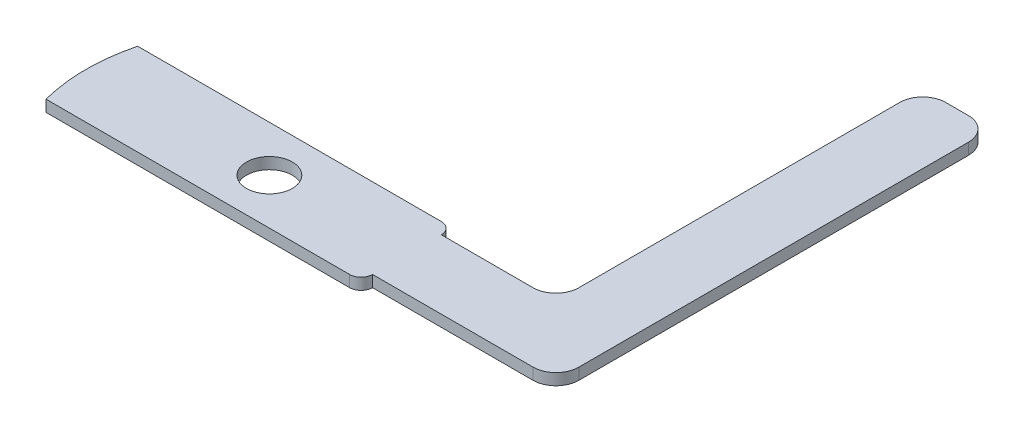
SolidWorks part; units mm, degrees
ref_plane "Front Plane" through (0, 0, 0) normal (0, 0, 1) x (1, 0, 0)
ref_plane "Top Plane" through (0, 0, 0) normal (0, 1, 0) x (1, 0, 0)
ref_plane "Right Plane" through (0, 0, 0) normal (1, 0, 0) x (0, 0, -1)
sketch "Sketch1" plane through (0, 0, 0) normal (0, 1, 0) x (1, 0, 0)
  line L0 (0, 6.35) -> (-31.75, 6.35) construction
  line L1 (0, 0) -> (-31.75, 0)
  line L2 (0, 0) -> (0, 12.7)
  line L3 (0, 12.7) -> (-31.75, 12.7)
  line L4 (-31.75, 0) -> (-31.75, 12.7) construction
  line L5 (0, 12.7) -> (12.7, 12.7)
  line L6 (12.7, 12.7) -> (12.7, 11.1125)
  line L7 (12.7, 11.1125) -> (28.575, 11.1125)
  line L8 (38.1, 11.1125) -> (38.1, 1.5875)
  line L9 (38.1, 1.5875) -> (12.7, 1.5875)
  line L10 (12.7, 1.5875) -> (12.7, 0)
  line L11 (12.7, 0) -> (0, 0)
  line L12 (38.1, 11.1125) -> (38.1, 61.9125)
  line L13 (38.1, 61.9125) -> (28.575, 61.9125)
  line L14 (28.575, 61.9125) -> (28.575, 11.1125)
  line L15 (28.575, 11.1125) -> (38.1, 11.1125) construction
  circle A0 centre (-6.35, 6.35) radius 3.175
  arc A1 (-30.9434, 12.7) -> (-30.9434, 0) centre (-6.35, 6.35) ccw
  dimension "D4" = 6.35
  dimension "D1" = 12.7
  dimension "D2" = 31.75
  dimension "D3" = 6.35
  dimension "D5" = 12.7
  dimension "D6" = 25.4
  dimension "D7" = 9.525
  dimension "D8" = 50.8
extrude "Boss-Extrude1" add sketch "Sketch1" along normal blind 1.5875 contours L2 L0 A0 L4 L1 | L0 L2 L3 L4 A0 | L11 L10 L9 L8 L6 L5 L2 region at (-16.5503, 0, -6.35) region at (0.727, 0, -6.35)
fillet "Fillet1" radius 3.175 4 edges at (38.1, 0.7937, -61.9125) (28.575, 0.7937, -61.9125) (28.575, 0.7937, -11.1125) (38.1, 0.7937, -1.5875)
fillet "Fillet2" radius 1.5875 2 edges at (12.7, 0.7937, 0) (12.7, 0.7937, -12.7)
